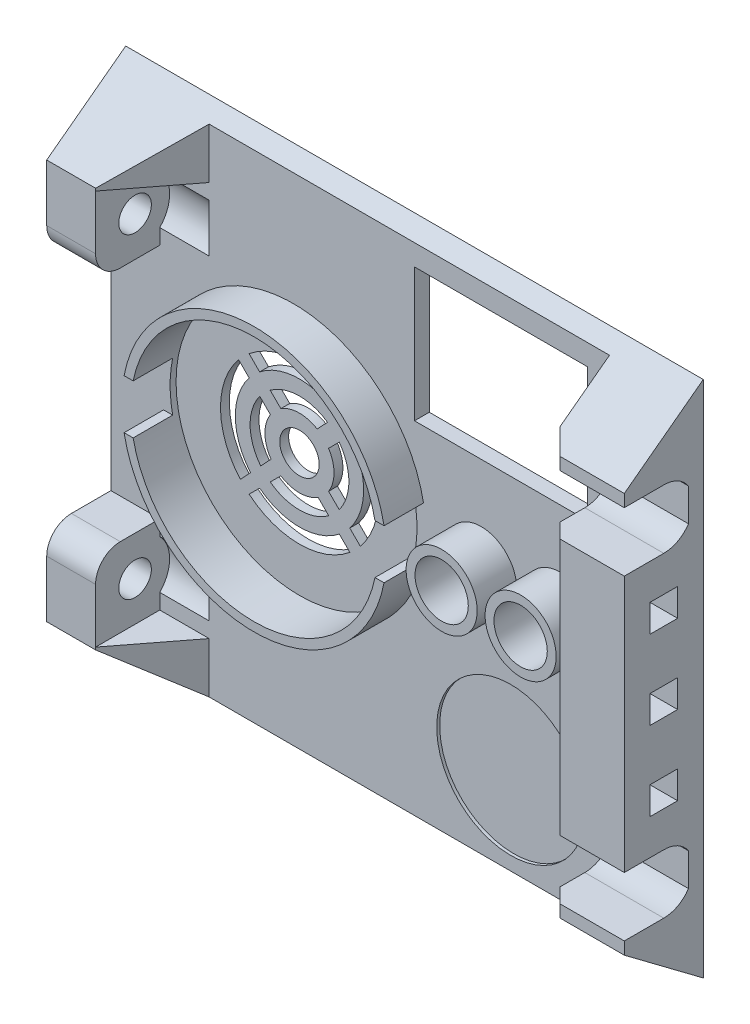
SolidWorks part; units mm, degrees
ref_plane "Plano frontal" through (0, 0, 0) normal (0, 0, 1) x (1, 0, 0)
ref_plane "Plano superior" through (0, 0, 0) normal (0, 1, 0) x (1, 0, 0)
ref_plane "Plano direito" through (0, 0, 0) normal (1, 0, 0) x (0, 0, -1)
sketch "Esboço1" plane through (0, 0, 0) normal (0, 0, 1) x (1, 0, 0)
  line L0 (-5, 0) -> (5, 0) construction
  line L1 (25, 0) -> (-25, 0) construction
  line L2 (0, 0) -> (0, -12.5) construction
  line L3 (25, -12.5) -> (-25, -12.5) construction
  line L4 (-21, 0) -> (-5, 0) construction
  line L5 (-25, -12.5) -> (-25, 12.5)
  line L6 (-25, 12.5) -> (25, 12.5)
  line L7 (0, 12.5) -> (0, 0) construction
  line L8 (20, -12.5) -> (-20, -12.5) construction
  line L12 (-15, -12.5) -> (15, -12.5)
  line L23 (21, 0) -> (5, 0) construction
  line L31 (25, -12.5) -> (25, 12.5)
  line L32 (-25, -12.5) -> (-15, -12.5)
  line L33 (15, -12.5) -> (25, -12.5)
  circle A0 centre (-13, 0) radius 8.3
  circle A1 centre (13, 0) radius 8.3
extrude "Ressalto-extrusão1" add sketch "Esboço1" along normal blind 1.5
sketch "Esboço2" plane through (0, 0, 1.5) normal (0, 0, 1) x (1, 0, 0)
  line L0 (-20, -12.5) -> (-25, -12.5)
  line L1 (0, -12.5) -> (0, 12.5) construction
  line L2 (20, -12.5) -> (-20, -12.5) construction
  line L3 (-25, -12.5) -> (25, -12.5) construction
  line L4 (22, -2.5) -> (22, -9.5)
  line L5 (-25, 12.5) -> (-25, -12.5) construction
  line L6 (-22, -9.5) -> (-15, -9.5)
  line L7 (-15, -9.5) -> (-15, -12.5)
  line L8 (-15, -12.5) -> (-20, -12.5)
  line L9 (-25, -12.5) -> (-25, -2.5)
  line L10 (-25, -2.5) -> (-22, -2.5)
  line L11 (-22, -2.5) -> (-22, -9.5)
  line L12 (25, -2.5) -> (22, -2.5)
  line L13 (25, -12.5) -> (25, -2.5)
  line L14 (15, -12.5) -> (20, -12.5)
  line L15 (25, 12.5) -> (-25, 12.5) construction
  line L16 (15, -9.5) -> (15, -12.5)
  line L17 (-25, 0) -> (25, 0) construction
  line L18 (25, -12.5) -> (25, 12.5) construction
  line L19 (22, -9.5) -> (15, -9.5)
  line L20 (20, -12.5) -> (25, -12.5)
  line L21 (20, 12.5) -> (-20, 12.5) construction
  line L22 (20, 12.5) -> (25, 12.5)
  line L23 (22, 9.5) -> (15, 9.5)
  line L24 (15, 9.5) -> (15, 12.5)
  line L25 (15, 12.5) -> (20, 12.5)
  line L26 (25, 12.5) -> (25, 2.5)
  line L27 (25, 2.5) -> (22, 2.5)
  line L28 (-22, 2.5) -> (-22, 9.5)
  line L29 (-25, 2.5) -> (-22, 2.5)
  line L30 (-25, 12.5) -> (-25, 2.5)
  line L31 (-15, 12.5) -> (-20, 12.5)
  line L32 (-15, 9.5) -> (-15, 12.5)
  line L33 (-22, 9.5) -> (-15, 9.5)
  line L34 (22, 2.5) -> (22, 9.5)
  line L35 (-20, 12.5) -> (-25, 12.5)
extrude "Ressalto-extrusão2" add sketch "Esboço2" along normal blind 6
sketch "Esboço3" plane through (0, -12.5, 0) normal (0, -1, 0) x (1, 0, 0)
  line L0 (-25, 3.75) -> (-15, 3.75) construction
  line L1 (-25, 7.5) -> (-25, 0) construction
  line L2 (-15, 7.5) -> (-15, 1.5) construction
  line L3 (-15, 3.75) -> (-20, 3.75) construction
  line L4 (-20, 3.75) -> (-20, 7.5) construction
  line L5 (-25, 7.5) -> (-15, 7.5) construction
  line L6 (0, 0) -> (0, 8.9122) construction
  line L7 (-21.4, 2.35) -> (-18.6, 2.35)
  line L8 (-21.4, 2.35) -> (-21.4, 5.15)
  line L9 (-21.4, 5.15) -> (-18.6, 5.15)
  line L10 (-18.6, 2.35) -> (-18.6, 5.15)
  line L11 (-21.4, 2.35) -> (-18.6, 5.15) construction
  line L12 (-21.4, 5.15) -> (-18.6, 2.35) construction
  line L13 (-25, 0) -> (25, 0) construction
  line L14 (21.4, 5.15) -> (18.6, 2.35) construction
  line L15 (21.4, 2.35) -> (18.6, 5.15) construction
  line L16 (18.6, 2.35) -> (18.6, 5.15)
  line L17 (21.4, 5.15) -> (18.6, 5.15)
  line L18 (21.4, 2.35) -> (21.4, 5.15)
  line L19 (21.4, 2.35) -> (18.6, 2.35)
extrude "Corte-extrusão1" cut sketch "Esboço3" against normal through all
sketch "Esboço4" plane through (-25, 0, 0) normal (-1, 0, 0) x (0, 0, 1)
  line L2 (3.75, 2.5) -> (3.75, 12.5) construction
  line L5 (3.75, -2.5) -> (3.75, -12.5) construction
  line L9 (0, 12.5) -> (7.5, 12.5) construction
  line L10 (5.15, 8.9) -> (2.35, 8.9)
  line L11 (5.15, 8.9) -> (5.15, 6.1)
  line L12 (5.15, 6.1) -> (2.35, 6.1)
  line L13 (2.35, 8.9) -> (2.35, 6.1)
  line L14 (5.15, 8.9) -> (2.35, 6.1) construction
  line L15 (5.15, 6.1) -> (2.35, 8.9) construction
  line L16 (5.15, -6.1) -> (2.35, -6.1)
  line L17 (5.15, -6.1) -> (5.15, -8.9)
  line L18 (5.15, -8.9) -> (2.35, -8.9)
  line L19 (2.35, -6.1) -> (2.35, -8.9)
  line L20 (5.15, -6.1) -> (2.35, -8.9) construction
  line L21 (5.15, -8.9) -> (2.35, -6.1) construction
  point P12 (3.75, 7.5)
  point P17 (3.75, -7.5)
  point P26 (3.75, 12.5)
extrude "Corte-extrusão2" cut sketch "Esboço4" against normal through all
sketch "Esboço6" plane through (0, 0, 0) normal (0, 0, -1) x (-1, 0, 0)
  line L0 (-25, 12.5) -> (-25, -12.5)
  line L1 (-30, -12.5) -> (-25, -12.5)
  line L2 (-30, -12.5) -> (-30, 12.5)
  line L3 (-30, 12.5) -> (-25, 12.5)
  line L4 (30, -12.5) -> (30, 12.5)
  line L5 (-30, -12.5) -> (30, 12.5) construction
  line L6 (-30, 12.5) -> (30, -12.5) construction
  line L7 (25, 12.5) -> (25, -12.5)
  line L8 (25, 12.5) -> (30, 12.5)
  line L9 (25, -12.5) -> (30, -12.5)
  point P0 (0, 0)
extrude "Ressalto-extrusão5" add sketch "Esboço6" against normal up to surface (7.5 mm away) up to face at (20.6667, -8.1667, 7.5)
sketch "Esboço7" plane through (30, 0, 0) normal (1, 0, 0) x (0, 0, -1)
  line L0 (-2.35, -6.1) -> (-5.15, -6.1) construction
  line L1 (-2.35, -8.9) -> (-2.35, -6.1) construction
  line L2 (-5.15, -8.9) -> (-2.35, -8.9) construction
  line L3 (-5.15, -6.1) -> (-5.15, -8.9) construction
  line L4 (-2.35, -6.1) -> (-5.15, -6.1)
  line L5 (-2.35, -8.9) -> (-2.35, -6.1)
  line L6 (-5.15, -8.9) -> (-2.35, -8.9)
  line L7 (-5.15, -6.1) -> (-5.15, -8.9)
  line L8 (-2.35, 6.1) -> (-2.35, 8.9) construction
  line L9 (-2.35, 8.9) -> (-5.15, 8.9) construction
  line L10 (-5.15, 8.9) -> (-5.15, 6.1) construction
  line L11 (-5.15, 6.1) -> (-2.35, 6.1) construction
  line L12 (-2.35, 6.1) -> (-2.35, 8.9)
  line L13 (-2.35, 8.9) -> (-5.15, 8.9)
  line L14 (-5.15, 8.9) -> (-5.15, 6.1)
  line L15 (-5.15, 6.1) -> (-2.35, 6.1)
extrude "Corte-extrusão3" cut sketch "Esboço7" against normal up to surface (60 mm away) up to face at (-30, 0, 3.75)
sketch "Esboço5" plane through (0, 0, 1.5) normal (0, 0, 1) x (1, 0, 0)
  line L0 (-9, -7.2726) -> (-9, -8.3958)
  line L1 (-17, -7.2726) -> (-17, -8.3958)
  line L2 (-17, 8.3958) -> (-17, 7.2726)
  line L3 (9, -7.2726) -> (9, -8.3958)
  line L4 (-9, 8.3958) -> (-9, 7.2726)
  line L8 (17, 8.3958) -> (17, 7.2726)
  line L10 (9, 8.3958) -> (9, 7.2726)
  line L13 (17, -7.2726) -> (17, -8.3958)
  circle A0 centre (-13, 0) radius 8.3 construction
  circle A1 centre (13, 0) radius 8.3 construction
  arc A2 (-17, 7.2726) -> (-17, -7.2726) centre (-13, 0) ccw
  arc A3 (17, -7.2726) -> (17, 7.2726) centre (13, 0) ccw
  arc A4 (-17, 8.3958) -> (-17, -8.3958) centre (-13, 0) ccw
  arc A5 (17, -8.3958) -> (17, 8.3958) centre (13, 0) ccw
  circle A6 centre (-13, 0) radius 8.3 construction
  circle A7 centre (-13, 0) radius 9.3 construction
  circle A8 centre (13, 0) radius 8.3 construction
  circle A9 centre (13, 0) radius 9.3 construction
  arc A12 (-9, -8.3958) -> (-9, 8.3958) centre (-13, 0) ccw
  arc A13 (-9, -7.2726) -> (-9, 7.2726) centre (-13, 0) ccw
  arc A14 (9, 7.2726) -> (9, -7.2726) centre (13, 0) ccw
  arc A15 (9, 8.3958) -> (9, -8.3958) centre (13, 0) ccw
  dimension "D1" = 1
  dimension "D2" = 1
extrude "Ressalto-extrusão3" add sketch "Esboço5" along normal blind 10
sketch "Esboço8" plane through (0, 0, 0) normal (0, 0, -1) x (-1, 0, 0)
  line L1 (30, 26.25) -> (-30, 26.25)
  line L2 (30, 26.25) -> (30, -26.25)
  line L3 (30, -26.25) -> (-30, -26.25)
  line L4 (-30, 26.25) -> (-30, -26.25)
  line L5 (30, 26.25) -> (-30, -26.25) construction
  line L6 (30, -26.25) -> (-30, 26.25) construction
  circle A0 centre (13, 0) radius 8.3
  circle A1 centre (-13, 0) radius 8.3
  point P6 (0, 0)
extrude "Ressalto-extrusão6" add sketch "Esboço8" against normal blind 1.5
sketch "Esboço9" plane through (0, 0, 1.5) normal (0, 0, 1) x (1, 0, 0)
  line L12 (-15, -12.5) -> (-15, -9.5)
  line L13 (-15, -9.5) -> (-22, -9.5)
  line L14 (-22, -9.5) -> (-22, -2.5)
  line L15 (-22, -2.5) -> (-25, -2.5)
  line L16 (-25, -2.5) -> (-25, 2.5)
  line L17 (-25, 2.5) -> (-22, 2.5)
  line L18 (-22, 2.5) -> (-22, 9.5)
  line L19 (-22, 9.5) -> (-15, 9.5)
  line L20 (-15, 9.5) -> (-15, 12.5)
  line L21 (-15, 12.5) -> (-30, 12.5)
  line L22 (-30, 12.5) -> (-30, -12.5)
  line L23 (-30, -12.5) -> (-15, -12.5)
  line L24 (-15, -12.5) -> (-15, -9.5)
  line L25 (-15, -9.5) -> (-22, -9.5)
  line L26 (-22, -9.5) -> (-22, -2.5)
  line L27 (-22, -2.5) -> (-25, -2.5)
  line L28 (-25, -2.5) -> (-25, 2.5)
  line L29 (-25, 2.5) -> (-22, 2.5)
  line L30 (-22, 2.5) -> (-22, 9.5)
  line L31 (-22, 9.5) -> (-15, 9.5)
  line L32 (-15, 9.5) -> (-15, 12.5)
  line L33 (-15, 12.5) -> (-30, 12.5)
  line L34 (-30, 12.5) -> (-30, -12.5)
  line L35 (-30, -12.5) -> (-15, -12.5)
  dimension "D1" = 0
extrude "Corte-extrusão4" cut sketch "Esboço9" along normal through all
sketch "Esboço10" plane through (0, 0, 1.5) normal (0, 0, 1) x (1, 0, 0)
  line L0 (-24.3, -26.25) -> (-24.3, 26.25)
  line L2 (-24.3, 26.25) -> (-22.3, 26.25)
  line L4 (-22.3, 12) -> (-17.3, 12)
  line L5 (-17.3, 12) -> (-17.3, -12)
  line L6 (-17.3, 0) -> (-24.3, 0) construction
  line L7 (-22.3, 20) -> (-22.3, 12)
  line L8 (-22.3, -20) -> (-22.3, -12)
  line L9 (-22.3, -12) -> (-17.3, -12)
  line L10 (-24.3, -26.25) -> (-22.3, -26.25)
  line L11 (-22.3, 12) -> (-22.3, 16) construction
  line L12 (-22.3, 16) -> (-22.3, 20) construction
  line L13 (-22.3, 20) -> (-17.3, 20)
  line L14 (-17.3, 20) -> (-17.3, 26.25)
  line L15 (-17.3, 26.25) -> (-22.3, 26.25)
  line L16 (-17.3, -26.25) -> (-22.3, -26.25)
  line L17 (-17.3, -20) -> (-17.3, -26.25)
  line L18 (-22.3, -20) -> (-17.3, -20)
  line L19 (-24.3, 0) -> (-22.3, 0) construction
  arc A0 (-17, 8.3958) -> (-17, -8.3958) centre (-13, 0) ccw construction
  point P22 (-22.3, 0)
  dimension "D1" = 12
extrude "Ressalto-extrusão7" add sketch "Esboço10" along normal blind 6.5
sketch "Esboço11" plane through (0, -26.25, 0) normal (0, -1, 0) x (1, 0, 0)
  line L0 (-22.3, 8) -> (-17.3, 8)
  line L1 (-17.3, 8) -> (-17.3, 1.5)
  line L2 (-22.3, 8) -> (-17.3, 1.5)
sketch "Esboço12" plane through (-24.3, 0, 0) normal (-1, 0, 0) x (0, 0, 1)
  line L0 (4, 0) -> (4, 16) construction
  line L1 (0, -26.25) -> (0, 26.25) construction
  line L3 (0, 0) -> (8, 0) construction
  circle A0 centre (4, 16) radius 1.65
  circle A1 centre (4, -16) radius 1.65
  dimension "D1" = 4
sketch "Esboço14" plane through (0, 0, 1.5) normal (0, 0, 1) x (1, 0, 0)
  line L4 (-30, -26.25) -> (-24.3, -26.25)
  line L5 (-24.3, -26.25) -> (-24.3, 26.25)
  line L6 (-24.3, 26.25) -> (-30, 26.25)
  line L7 (-30, 26.25) -> (-30, -26.25)
  line L8 (-30, -26.25) -> (-24.3, -26.25)
  line L9 (-24.3, -26.25) -> (-24.3, 26.25)
  line L10 (-24.3, 26.25) -> (-30, 26.25)
  line L11 (-30, 26.25) -> (-30, -26.25)
  dimension "D1" = 0
extrude "Corte-extrusão8" cut sketch "Esboço14" against normal blind 4.5
sketch "Esboço15" plane through (0, 0, 8) normal (0, 0, 1) x (1, 0, 0)
  line L1 (-17.3, -7.0993) -> (-17.3, 7.0993)
  line L2 (-17.3, -7.0993) -> (-17.3, 7.0993)
  arc A1 (-17.3, 7.0993) -> (-17.3, -7.0993) centre (-13, 0) ccw
  arc A2 (-17.3, 7.0993) -> (-17.3, -7.0993) centre (-13, 0) ccw
  dimension "D1" = 0
extrude "Corte-extrusão9" cut sketch "Esboço15" against normal through all
extrude "Corte-extrusão13" cut sketch "Esboço11" against normal up to surface (6.25 mm away) up to face at (-19.8, -20, 4.75)
sketch "Esboço17" plane through (0, 26.25, 0) normal (0, 1, 0) x (1, 0, 0)
  line L0 (-17.3, -1.5) -> (-17.3, -8)
  line L1 (-17.3, -8) -> (-22.3, -8)
  line L2 (-17.3, -8) -> (-24.3, -8) construction
  line L3 (-22.3, -8) -> (-17.3, -1.5)
extrude "Corte-extrusão14" cut sketch "Esboço17" against normal up to surface (6.25 mm away) up to face at (-19.8, 20, 4.75)
extrude "Corte-extrusão15" cut sketch "Esboço12" against normal blind 4.5
sketch "Esboço19" plane through (-24.3, 0, 0) normal (-1, 0, 0) x (0, 0, 1)
  line L0 (0, 26.25) -> (8, 26.25)
  line L1 (8, 26.25) -> (8, 20.25)
  line L2 (8, 26.25) -> (8, -26.25) construction
  line L3 (8, 20.25) -> (0, 26.25)
  line L4 (0, 0) -> (8, 0) construction
  line L5 (8, -20.25) -> (0, -26.25)
  line L6 (8, -26.25) -> (8, -20.25)
  line L7 (0, -26.25) -> (8, -26.25)
extrude "Corte-extrusão17" cut sketch "Esboço19" against normal through all
sketch "Esboço20" plane through (-22.3, 0, 0) normal (1, 0, 0) x (0, 0, -1)
  circle A0 centre (-4, -16) radius 3.5
  circle A1 centre (-4, 16) radius 3.5
extrude "Corte-extrusão18" cut sketch "Esboço20" along normal blind 5
sketch "Esboço21" plane through (-24.3, 0, 0) normal (-1, 0, 0) x (0, 0, 1)
  line L4 (0, 26.25) -> (0, -26.25)
  line L5 (0, -26.25) -> (8, -20.25)
  line L6 (8, -20.25) -> (8, 20.25)
  line L7 (8, 20.25) -> (0, 26.25)
  line L8 (0, 26.25) -> (0, -26.25)
  line L9 (0, -26.25) -> (8, -20.25)
  line L10 (8, -20.25) -> (8, 20.25)
  line L11 (8, 20.25) -> (0, 26.25)
  circle A0 centre (4, -16) radius 1.65 construction
  circle A1 centre (4, -16) radius 1.65
  circle A2 centre (4, 16) radius 1.65 construction
  circle A3 centre (4, 16) radius 1.65
  dimension "D1" = 0
extrude "Ressalto-extrusão8" add sketch "Esboço21" along normal blind 2.95
sketch "Esboço22" plane through (30, 0, 0) normal (1, 0, 0) x (0, 0, -1)
  line L0 (-2.35, -6.1) -> (-5.15, -6.1) construction
  line L1 (-2.35, -8.9) -> (-2.35, -6.1) construction
  line L2 (-5.15, -8.9) -> (-2.35, -8.9) construction
  line L3 (-5.15, -6.1) -> (-5.15, -8.9) construction
  line L4 (-2.35, 8.9) -> (-5.15, 8.9) construction
  line L5 (-5.15, 8.9) -> (-5.15, 6.1) construction
  line L6 (-2.35, 6.1) -> (-2.35, 8.9) construction
  line L7 (-5.15, 6.1) -> (-2.35, 6.1) construction
  line L8 (-1.5, -25.125) -> (0, -26.25)
  line L9 (0, -26.25) -> (0, 26.25)
  line L10 (0, 26.25) -> (-1.5, 25.125)
  line L11 (-1.5, 25.125) -> (-1.5, 12.5)
  line L12 (-1.5, 12.5) -> (-7.5, 12.5)
  line L13 (-7.5, 12.5) -> (-7.5, -12.5)
  line L14 (-7.5, -12.5) -> (-1.5, -12.5)
  line L15 (-1.5, -12.5) -> (-1.5, -25.125)
  line L16 (-1.5, -25.125) -> (0, -26.25)
  line L17 (0, -26.25) -> (0, 26.25)
  line L18 (0, 26.25) -> (-1.5, 25.125)
  line L19 (-1.5, 25.125) -> (-1.5, 12.5)
  line L20 (-1.5, 12.5) -> (-7.5, 12.5)
  line L21 (-7.5, 12.5) -> (-7.5, -12.5)
  line L22 (-7.5, -12.5) -> (-1.5, -12.5)
  line L23 (-1.5, -12.5) -> (-1.5, -25.125)
  line L24 (-2.35, -6.1) -> (-5.15, -6.1)
  line L25 (-2.35, -8.9) -> (-2.35, -6.1)
  line L26 (-5.15, -8.9) -> (-2.35, -8.9)
  line L27 (-5.15, -6.1) -> (-5.15, -8.9)
  line L28 (-2.35, 8.9) -> (-5.15, 8.9)
  line L29 (-5.15, 8.9) -> (-5.15, 6.1)
  line L30 (-2.35, 6.1) -> (-2.35, 8.9)
  line L31 (-5.15, 6.1) -> (-2.35, 6.1)
  dimension "D1" = 0
extrude "Ressalto-extrusão9" add sketch "Esboço22" along normal blind 1.25
sketch "Esboço23" plane through (0, 0, 7.5) normal (0, 0, 1) x (1, 0, 0)
  line L12 (25, -2.5) -> (22, -2.5)
  line L13 (22, -2.5) -> (22, -9.5)
  line L14 (22, -9.5) -> (15, -9.5)
  line L15 (15, -9.5) -> (15, -12.5)
  line L16 (15, -12.5) -> (31.25, -12.5)
  line L17 (31.25, -12.5) -> (31.25, 12.5)
  line L18 (31.25, 12.5) -> (15, 12.5)
  line L19 (15, 12.5) -> (15, 9.5)
  line L20 (15, 9.5) -> (22, 9.5)
  line L21 (22, 9.5) -> (22, 2.5)
  line L22 (22, 2.5) -> (25, 2.5)
  line L23 (25, 2.5) -> (25, -2.5)
  line L24 (25, -2.5) -> (22, -2.5)
  line L25 (22, -2.5) -> (22, -9.5)
  line L26 (22, -9.5) -> (15, -9.5)
  line L27 (15, -9.5) -> (15, -12.5)
  line L28 (15, -12.5) -> (31.25, -12.5)
  line L29 (31.25, -12.5) -> (31.25, 12.5)
  line L30 (31.25, 12.5) -> (15, 12.5)
  line L31 (15, 12.5) -> (15, 9.5)
  line L32 (15, 9.5) -> (22, 9.5)
  line L33 (22, 9.5) -> (22, 2.5)
  line L34 (22, 2.5) -> (25, 2.5)
  line L35 (25, 2.5) -> (25, -2.5)
  dimension "D1" = 0
extrude "Corte-extrusão19" cut sketch "Esboço23" against normal up to surface (6 mm away) up to face at (13, 0, 1.5)
sketch "Esboço24" plane through (0, 0, 1.5) normal (0, 0, 1) x (1, 0, 0)
  line L0 (31.25, -25.125) -> (-17.3, -25.125) construction
  line L1 (31.25, 25.125) -> (23.25, 25.125)
  line L2 (31.25, 25.125) -> (31.25, -25.125)
  line L3 (31.25, -25.125) -> (23.25, -25.125)
  line L4 (23.25, 25.125) -> (23.25, -25.125)
extrude "Ressalto-extrusão10" add sketch "Esboço24" along normal up to surface (6.5 mm away) up to face at (-21.875, 0, 8)
sketch "Esboço25" plane through (0, 25.125, 0) normal (0, 1, 0) x (1, 0, 0)
  line L1 (23.25, -8) -> (23.25, -1.5) construction
  line L2 (23.25, -6.5) -> (23.25, -8)
  line L3 (23.25, -8) -> (24.75, -8)
  line L4 (23.25, -8) -> (31.25, -8) construction
  line L5 (24.75, -8) -> (23.25, -6.5)
extrude "Corte-extrusão20" cut sketch "Esboço25" against normal through all
sketch "Esboço26" plane through (31.25, 0, 0) normal (1, 0, 0) x (0, 0, -1)
  line L0 (-8, 0) -> (0, 0) construction
  line L1 (-8, 25.125) -> (-8, -25.125) construction
  line L2 (0, 0) -> (-4, 0) construction
  line L3 (-4, 0) -> (-4, -8) construction
  line L4 (-2.6, 1.4) -> (-5.4, 1.4)
  line L5 (-2.6, -6.6) -> (-5.4, -6.6)
  line L6 (-2.6, -6.6) -> (-2.6, -9.4)
  line L7 (-2.6, -9.4) -> (-5.4, -9.4)
  line L8 (-5.4, -6.6) -> (-5.4, -9.4)
  line L9 (-2.6, -6.6) -> (-5.4, -9.4) construction
  line L10 (-2.6, -9.4) -> (-5.4, -6.6) construction
  line L11 (-2.6, 1.4) -> (-2.6, -1.4)
  line L12 (-2.6, -1.4) -> (-5.4, -1.4)
  line L13 (-5.4, 1.4) -> (-5.4, -1.4)
  line L14 (-2.6, 1.4) -> (-5.4, -1.4) construction
  line L15 (-2.6, -1.4) -> (-5.4, 1.4) construction
  line L16 (-2.6, 9.4) -> (-5.4, 9.4)
  line L17 (-2.6, 9.4) -> (-2.6, 6.6)
  line L18 (-2.6, 6.6) -> (-5.4, 6.6)
  line L19 (-5.4, 9.4) -> (-5.4, 6.6)
  line L20 (-2.6, 9.4) -> (-5.4, 6.6) construction
  line L21 (-2.6, 6.6) -> (-5.4, 9.4) construction
  dimension "D1" = 3
extrude "Corte-extrusão21" cut sketch "Esboço26" against normal up to next
sketch "Esboço27" plane through (31.25, 0, 0) normal (1, 0, 0) x (0, 0, -1)
  line L0 (-4, 19) -> (-8, 19)
  line L1 (-8, -20.25) -> (-8, -25.125)
  line L2 (-8, 25.125) -> (-8, -25.125) construction
  line L3 (-8, 25.125) -> (-8, 20.25)
  line L4 (-8, 19) -> (-8, 13)
  line L5 (-8, 13) -> (-4, 13)
  line L6 (-4, -13) -> (-8, -13)
  line L7 (-8, -13) -> (-8, -19)
  line L8 (-8, -19) -> (-4, -19)
  line L9 (-1.5, 25.125) -> (-1.5, -25.125) construction
  line L10 (-1.5, 17.6583) -> (-1.5, 14.3417)
  line L11 (-1.5, -14.3417) -> (-1.5, -17.6583)
  line L13 (-1.5, 25.125) -> (-8, 20.25) construction
  line L17 (-8, -20.25) -> (-1.5, -25.125) construction
  line L21 (-1.5, 25.125) -> (-8, 20.25)
  line L25 (-8, -20.25) -> (-1.5, -25.125)
  line L28 (-1.5, 25.125) -> (-8, 25.125)
  line L30 (-1.5, -25.125) -> (-8, -25.125)
  circle A0 centre (-4, -16) radius 1.65 construction
  circle A1 centre (-4, 16) radius 1.65 construction
  circle A2 centre (-4, -16) radius 1.65 construction
  circle A3 centre (-4, 16) radius 1.65 construction
  arc A4 (-4, -19) -> (-1.5, -17.6583) centre (-4, -16) ccw
  arc A5 (-4, 13) -> (-1.5, 14.3417) centre (-4, 16) ccw
  arc A6 (-1.5, 17.6583) -> (-4, 19) centre (-4, 16) ccw
  arc A7 (-1.5, -14.3417) -> (-4, -13) centre (-4, -16) ccw
extrude "Corte-extrusão22" cut sketch "Esboço27" against normal up to next
sketch "Esboço28" plane through (0, 0, 8) normal (0, 0, 1) x (1, 0, 0)
  line L0 (-27.25, -12) -> (-27.25, 12)
  line L1 (-27.25, -20.25) -> (-27.25, 20.25) construction
  line L2 (-27.25, 12) -> (-24.8, 12)
  line L3 (-22.3, 9.5) -> (-22.3, -9.5)
  line L4 (-24.8, -12) -> (-27.25, -12)
  line L5 (-27.25, -12) -> (-27.25, 12)
  arc A0 (-24.8, 12) -> (-22.3, 9.5) centre (-24.8, 9.5) cw
  arc A1 (-22.3, -9.5) -> (-24.8, -12) centre (-24.8, -9.5) cw
  point P9 (-22.3, 12)
  line M2 (-27.25, 20.25) -> (-27.25, -20.25)
  dimension "D1" = 2.5
extrude "Corte-extrusão23" cut sketch "Esboço28" against normal up to surface (6.5 mm away) contours A1 L3 A0 L2 L4 M2 region at (-24.8193, 0, 8) up to face at (13, 0, 1.5)
sketch "Esboço29" plane through (0, 0, 8) normal (0, 0, 1) x (1, 0, 0)
  line L0 (-19.8, -12) -> (-19.8, -12.4492)
  line L6 (-19.8, 12) -> (-19.8, 12.9071)
  line L7 (-19.8, 12.9071) -> (-15.7505, 12.9071)
  line L8 (-15.7505, 12.9071) -> (-15.7505, 9.5)
  line L9 (-15.7505, 9.5) -> (-17.3, 9.5)
  line L10 (-17.3, -9.5) -> (-15.2259, -9.5)
  line L11 (-15.2259, -9.5) -> (-15.2259, -14.1397)
  line L12 (-15.2259, -14.1397) -> (-19.8, -14.1397)
  line L13 (-19.8, -14.1397) -> (-19.8, -12.4492)
  arc A0 (-19.8, -12) -> (-17.3, -9.5) centre (-19.8, -9.5) ccw
  arc A1 (-19.8, 12) -> (-17.3, 9.5) centre (-19.8, 9.5) cw
  point P16 (-17.3, -12)
  point P19 (-17.3, 12)
  dimension "D1" = 2.5
extrude "Corte-extrusão24" cut sketch "Esboço29" against normal up to surface (6.5 mm away) up to face at (13, 0, 1.5)
sketch "Esboço30" plane through (0, 0, 8) normal (0, 0, 1) x (1, 0, 0)
  line L0 (-27.25, 12) -> (-17, 12)
  line L1 (-17, 12) -> (-17, 8.3958)
  line L2 (-27.25, -12) -> (-17, -12)
  line L3 (-17, -12) -> (-17, -8.3958)
  line L4 (-27.25, -12) -> (-27.25, 12)
  arc A0 (-17, 8.3958) -> (-17, -8.3958) centre (-13, 0) ccw construction
  arc A1 (-17, 8.3958) -> (-17, -8.3958) centre (-13, 0) ccw
extrude "Corte-extrusão25" cut sketch "Esboço30" against normal up to surface (6.5 mm away) up to face at (-6.4691, 0, 1.5)
sketch "Esboço31" plane through (-27.25, 0, 0) normal (-1, 0, 0) x (0, 0, 1)
  line L8 (5.5, -12) -> (8, -12)
  line L9 (8, -12) -> (8, -14.5)
  line L10 (5.5, 12) -> (8, 12)
  line L11 (8, 12) -> (8, 14.5)
  arc A0 (5.5, -12) -> (8, -14.5) centre (5.5, -14.5) cw
  arc A1 (5.5, 12) -> (8, 14.5) centre (5.5, 14.5) ccw
  point P18 (8, -12)
  point P21 (8, 12)
  dimension "D1" = 2.5
extrude "Corte-extrusão26" cut sketch "Esboço31" against normal up to surface (4.95 mm away) up to face at (-22.3, 16, 5.65)
sketch "Esboço33" plane through (0, 0, 1.5) normal (0, 0, 1) x (1, 0, 0)
  circle A0 centre (13, 0) radius 9.3
  circle A1 centre (-13, 0) radius 9.3
extrude "Corte-extrusão27" cut sketch "Esboço33" along normal through all
sketch "Esboço34" plane through (0, 0, 0) normal (0, 0, -1) x (-1, 0, 0)
  circle A0 centre (-13, 0) radius 8.3 construction
  circle A1 centre (13, 0) radius 8.3 construction
  circle A2 centre (-13, 0) radius 8.3
  circle A3 centre (13, 0) radius 8.3
extrude "Ressalto-extrusão11" add sketch "Esboço34" against normal up to surface (1.5 mm away) up to face at (-4.7, 0, 1.5)
sketch "Esboço35" plane through (0, 0, 1.5) normal (0, 0, 1) x (1, 0, 0)
  line L0 (-8.75, 0.25) -> (-8.75, -5.9027) construction
  line L1 (-8.75, 13.65) -> (-8.75, -13.4027) construction
  line L2 (-8.75, -13.4027) -> (-8.75, 0.1237) construction
  line L3 (3.4974, -2.25) -> (4.4147, -2.25)
  line L4 (23.25, -24.8777) -> (23.25, 25.125) construction
  line L5 (23.25, 25.125) -> (23.25, 0.1237) construction
  line L6 (-21.9147, 2.75) -> (-20.9974, 2.75)
  line L7 (23.25, 0.1237) -> (-8.75, 0.1237) construction
  line L8 (3.4974, 2.75) -> (4.4147, 2.75)
  line L9 (-21.9147, -2.25) -> (-20.9974, -2.25)
  line L10 (-27.25, 26.25) -> (31.25, 26.25) construction
  arc A0 (-20.9974, -2.25) -> (3.4974, -2.25) centre (-8.75, 0.25) ccw
  arc A1 (-21.9147, -2.25) -> (4.4147, -2.25) centre (-8.75, 0.25) ccw
  circle A2 centre (-8.75, -5.9027) radius 7.5 construction
  circle A3 centre (-8.75, 0.25) radius 12.5 construction
  circle A4 centre (-8.75, 0.25) radius 13.4 construction
  arc A5 (4.4147, 2.75) -> (-21.9147, 2.75) centre (-8.75, 0.25) ccw
  arc A6 (3.4974, 2.75) -> (-20.9974, 2.75) centre (-8.75, 0.25) ccw
  dimension "D1" = 25
  dimension "D2" = 0.9
  dimension "D3" = 15
  dimension "D4" = 26
  dimension "D5" = 32
extrude "Ressalto-extrusão12" add sketch "Esboço35" along normal blind 4
sketch "Esboço37" plane through (0, 0, 1.5) normal (0, 0, 1) x (1, 0, 0)
  line L0 (-9.2743, 0.7754) -> (-8.2186, -0.2802) construction
  line L1 (-15.7739, -6.16) -> (-2.7747, 7.7109)
  line L2 (-15.7739, -6.16) -> (-14.9362, -6.9977)
  line L3 (-14.9362, -6.9977) -> (-1.5011, 6.4373)
  line L4 (-2.7747, 7.7109) -> (-1.5011, 6.4373)
  line L5 (-14.9362, 7.498) -> (-1.5011, -5.9371)
  line L6 (-14.9362, 7.498) -> (-15.9968, 6.4373)
  line L7 (-15.9968, 6.4373) -> (-2.5618, -6.9977)
  line L8 (-1.5011, -5.9371) -> (-2.5618, -6.9977)
  line L9 (-8.2186, -0.2802) -> (-8.2186, 0.7804) construction
  line L10 (-8.2186, 0.7804) -> (-9.2793, -0.2802) construction
  circle A0 centre (-8.75, 0.25) radius 12.5 construction
  circle A1 centre (-8.75, 0.25) radius 2
  circle A2 centre (-8.75, 0.25) radius 3.5
  circle A3 centre (-8.75, 0.25) radius 5
  circle A4 centre (-8.75, 0.25) radius 6.5
  circle A5 centre (-8.75, 0.25) radius 8
  point P24 (-8.749, 0.2501)
  dimension "D1" = 1.5
  dimension "D2" = 1.5
  dimension "D3" = 1.5
  dimension "D4" = 1.5
extrude "Corte-extrusão31" cut sketch "Esboço37" against normal through all contours L7 A1 L1 | L5 A1 L7 L1 | L1 A1 L3 L7 | L1 L7 L3 L5 | L7 A1 L5 L3 | L3 A1 L1 L5 | L5 A1 L3 | L3 A1 L7 | L1 A1 L5 | L7 A3 L1 A2 | L5 A3 L3 A2 | L1 A3 L5 A2 | L3 A3 L7 A2 | L3 A5 L7 A4 | L5 A5 L3 A4 | L1 A5 L5 A4 | L7 A5 L1 A4 region at (-15.4502, 0.138, 1.5) region at (-8.7493, -6.4781, 1.5) region at (-12.7787, 0.1812, 1.5) region at (-8.8553, 7.0019, 1.5) region at (-8.7493, -3.7944, 1.5) region at (-2.0217, 0.2501, 1.5) region at (-10.3892, 0.2194, 1.5) region at (-9.6884, -0.7217, 1.5) region at (-8.8115, 4.307, 1.5) region at (-9.7061, 1.2001, 1.5) region at (-8.7436, 0.2505, 1.5) region at (-8.7492, -1.4006, 1.5) region at (-4.7054, 0.2501, 1.5) region at (-8.7719, 1.9071, 1.5) region at (-7.8042, 1.2176, 1.5) region at (-7.7934, -0.7056, 1.5) region at (-7.099, 0.2501, 1.5)
sketch "Esboço42" plane through (0, 0, 1.5) normal (0, 0, 1) x (1, 0, 0)
  circle A0 centre (-8.75, 0.25) radius 12.5
extrude "Corte-extrusão32" cut sketch "Esboço42" against normal blind 0.6
sketch "Esboço43" plane through (0, 0, 1.5) normal (0, 0, 1) x (1, 0, 0)
  line L0 (31.25, 13) -> (31.25, -13) construction
  line L1 (3.5, 23) -> (21, 23)
  line L2 (3.5, 23) -> (3.5, 9.5)
  line L3 (3.5, 9.5) -> (21, 9.5)
  line L4 (21, 23) -> (21, 9.5)
  line L5 (3.5, 23) -> (21, 9.5) construction
  line L6 (3.5, 9.5) -> (21, 23) construction
  line L7 (-27.25, 26.25) -> (31.25, 26.25) construction
  point P0 (12.25, 16.25)
  dimension "D1" = 17.5
  dimension "D2" = 13.5
  dimension "D3" = 19
  dimension "D4" = 10
extrude "Corte-extrusão33" cut sketch "Esboço43" against normal through all
sketch "Esboço44" plane through (0, 0, 1.5) normal (0, 0, 1) x (1, 0, 0)
  line L0 (31.25, -26.25) -> (-27.25, -26.25) construction
  line L1 (31.25, 13) -> (31.25, -13) construction
  circle A0 centre (13.25, -16.25) radius 7.5
  dimension "D1" = 15
  dimension "D2" = 10
  dimension "D3" = 18
extrude "Corte-extrusão34" cut sketch "Esboço44" against normal blind 0.3
sketch "Esboço45" plane through (0, 0, 1.5) normal (0, 0, 1) x (1, 0, 0)
  line L0 (31.25, -26.25) -> (31.25, 26.25) construction
  line L1 (31.25, -26.25) -> (31.25, 26.25) construction
  line L2 (31.25, 0) -> (18.25, 0) construction
  circle A0 centre (18.25, 0) radius 2.7
  circle A1 centre (10.25, 0) radius 2.7
  dimension "D1" = 13
  dimension "D2" = 2
extrude "Corte-extrusão35" cut sketch "Esboço45" against normal through all
sketch "Esboço46" plane through (0, 0, 1.2) normal (0, 0, 1) x (1, 0, 0)
  circle A2 centre (13.25, -16.25) radius 3
  dimension "D1" = 6
extrude "Corte-extrusão36" cut sketch "Esboço46" against normal through all
chamfer "Chanfro1" distance 1 angle 45 1 edges at (16.25, -16.25, 0)
sketch "Esboço47" plane through (0, 0, 1.2) normal (0, 0, 1) x (1, 0, 0)
  circle A0 centre (13.25, -16.25) radius 3 construction
  circle A1 centre (13.25, -16.25) radius 3
extrude "Ressalto-extrusão13" add sketch "Esboço47" against normal through all
chamfer "Chanfro2" distance 1 angle 45 1 edges at (16.25, -16.25, 0)
sketch "Esboço48" plane through (0, 0, 1.5) normal (0, 0, 1) x (1, 0, 0)
  circle A0 centre (10.25, 0) radius 2.7 construction
  circle A1 centre (18.25, 0) radius 2.7 construction
  circle A2 centre (10.25, 0) radius 2.7
  circle A3 centre (18.25, 0) radius 2.7
  circle A4 centre (10.25, 0) radius 3.6
  circle A5 centre (18.25, 0) radius 3.6
  dimension "D1" = 0.9
extrude "Ressalto-extrusão14" add sketch "Esboço48" along normal blind 4
